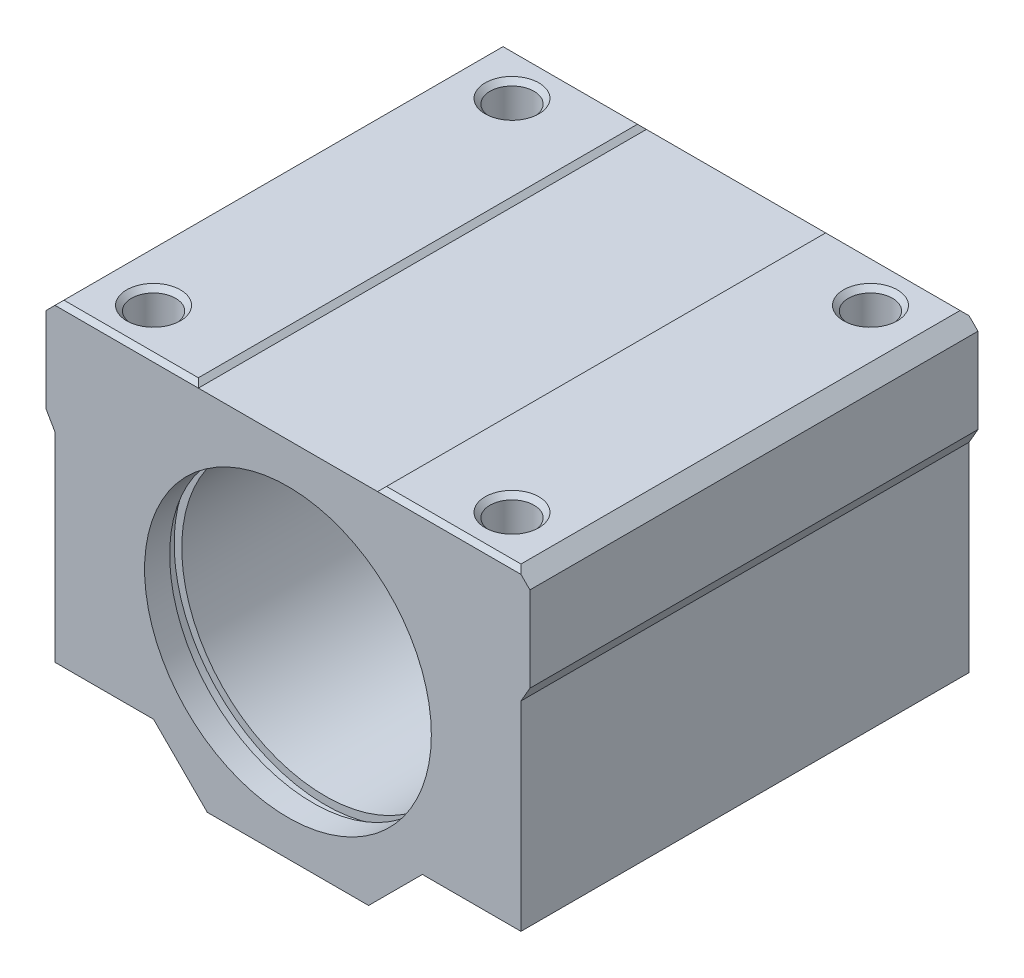
SolidWorks part; units mm, degrees
ref_plane "前视" through (0, 0, 0) normal (0, 0, 1) x (1, 0, 0)
ref_plane "上视" through (0, 0, 0) normal (0, 1, 0) x (1, 0, 0)
ref_plane "右视" through (0, 0, 0) normal (1, 0, 0) x (0, 0, -1)
sketch "草图1" plane through (0, 0, 0) normal (0, 0, 1) x (1, 0, 0)
  line L0 (-27, 19.5) -> (-27, 10)
  line L1 (-27, 10) -> (-26, 8.2679)
  line L2 (-26, 8.2679) -> (-26, -14)
  line L3 (-26, -14) -> (-15, -14)
  line L4 (-15, -14) -> (-9, -20)
  line L5 (-9, -20) -> (9, -20)
  line L6 (9, -20) -> (15, -14)
  line L7 (15, -14) -> (26, -14)
  line L8 (26, -14) -> (26, 8.2679)
  line L9 (26, 8.2679) -> (27, 10)
  line L10 (27, 10) -> (27, 19.5)
  line L11 (27, 19.5) -> (25.5, 21)
  line L12 (25.5, 21) -> (10.5, 21)
  line L13 (10.5, 21) -> (10, 20.5)
  line L14 (10, 20.5) -> (-10, 20.5)
  line L15 (-10, 20.5) -> (-10.5, 21)
  line L16 (-10.5, 21) -> (-25.5, 21)
  line L17 (-25.5, 21) -> (-27, 19.5)
extrude "凸台-拉伸1" add sketch "草图1" along normal blind 50
sketch "草图2" plane through (0, 0, 0) normal (1, 0, 0) x (0, 0, -1)
  line L0 (-62.5, -41) -> (12.5, -41)
  line L1 (12.5, -41) -> (12.5, 41)
  line L2 (12.5, 41) -> (-62.5, 41)
  line L3 (-62.5, 41) -> (-62.5, -41)
  line L4 (-50, -20) -> (0, -20)
  line L5 (0, -20) -> (0, 20.5)
  line L6 (0, 20.5) -> (-0.5, 21)
  line L7 (-0.5, 21) -> (-49.5, 21)
  line L8 (-49.5, 21) -> (-50, 20.5)
  line L9 (-50, 20.5) -> (-50, -20)
extrude "切除-拉伸1" cut sketch "草图2" along normal blind 27 and the other way blind 27
sketch "草图3" plane through (0, 0, 0) normal (1, 0, 0) x (0, 0, -1)
  line L0 (-50, 0) -> (-50, 16)
  line L1 (-50, 16) -> (-47.2, 16)
  line L2 (-47.2, 16) -> (-47.2, 16.85)
  line L3 (-47.2, 16.85) -> (-45.85, 16.85)
  line L4 (-45.85, 16.85) -> (-45.85, 16)
  line L5 (-45.85, 16) -> (-4.15, 16)
  line L6 (-4.15, 16) -> (-4.15, 16.85)
  line L7 (-4.15, 16.85) -> (-2.8, 16.85)
  line L8 (-2.8, 16.85) -> (-2.8, 16)
  line L9 (-2.8, 16) -> (0, 16)
  line L10 (0, 16) -> (0, 0)
  line L11 (0, 0) -> (-50, 0)
  line L12 (0, 0) -> (-50, 0) construction
revolve "切除-旋转1" cut sketch "草图3" angle 360 about L12 reverse direction yes
ref_plane "基准面1" through (20, 0, 0) normal (1, 0, 0) x (0, 0, -1)
sketch "草图4" plane through (20, 0, 0) normal (1, 0, 0) x (0, 0, -1)
  line L0 (-5, 21) -> (-2, 21)
  line L1 (-2, 21) -> (-2.5415, 20.4585)
  line L2 (-2.5415, 20.4585) -> (-2.5415, 9)
  line L3 (-2.5415, 9) -> (-2.4, 9)
  line L4 (-2.4, 9) -> (-2.4, -13.5)
  line L5 (-2.4, -13.5) -> (-2.1113, -14)
  line L6 (-2.1113, -14) -> (-5, -14)
  line L7 (-5, -14) -> (-5, 21)
  line L8 (-5, -14) -> (-5, 21) construction
revolve "切除-旋转2" cut sketch "草图4" angle 360 about L8 reverse direction yes
cosmetic thread "装饰螺纹线1" parameters "D1"=12, "D2"=6
sketch "草图5" plane through (20, 0, 0) normal (1, 0, 0) x (0, 0, -1)
  line L0 (-45, 21) -> (-42, 21)
  line L1 (-42, 21) -> (-42.5415, 20.4585)
  line L2 (-42.5415, 20.4585) -> (-42.5415, 9)
  line L3 (-42.5415, 9) -> (-42.4, 9)
  line L4 (-42.4, 9) -> (-42.4, -13.5)
  line L5 (-42.4, -13.5) -> (-42.1113, -14)
  line L6 (-42.1113, -14) -> (-45, -14)
  line L7 (-45, -14) -> (-45, 21)
  line L8 (-45, -14) -> (-45, 21) construction
revolve "切除-旋转3" cut sketch "草图5" angle 360 about L8 reverse direction yes
cosmetic thread "装饰螺纹线2" parameters "D1"=12, "D2"=6
ref_plane "基准面2" through (-20, 0, 0) normal (1, 0, 0) x (0, 0, -1)
sketch "草图6" plane through (-20, 0, 0) normal (1, 0, 0) x (0, 0, -1)
  line L0 (-5, 21) -> (-2, 21)
  line L1 (-2, 21) -> (-2.5415, 20.4585)
  line L2 (-2.5415, 20.4585) -> (-2.5415, 9)
  line L3 (-2.5415, 9) -> (-2.4, 9)
  line L4 (-2.4, 9) -> (-2.4, -13.5)
  line L5 (-2.4, -13.5) -> (-2.1113, -14)
  line L6 (-2.1113, -14) -> (-5, -14)
  line L7 (-5, -14) -> (-5, 21)
  line L8 (-5, -14) -> (-5, 21) construction
revolve "切除-旋转4" cut sketch "草图6" angle 360 about L8 reverse direction yes
cosmetic thread "装饰螺纹线3" parameters "D1"=12, "D2"=6
sketch "草图7" plane through (-20, 0, 0) normal (1, 0, 0) x (0, 0, -1)
  line L0 (-45, 21) -> (-42, 21)
  line L1 (-42, 21) -> (-42.5415, 20.4585)
  line L2 (-42.5415, 20.4585) -> (-42.5415, 9)
  line L3 (-42.5415, 9) -> (-42.4, 9)
  line L4 (-42.4, 9) -> (-42.4, -13.5)
  line L5 (-42.4, -13.5) -> (-42.1113, -14)
  line L6 (-42.1113, -14) -> (-45, -14)
  line L7 (-45, -14) -> (-45, 21)
  line L8 (-45, -14) -> (-45, 21) construction
revolve "切除-旋转5" cut sketch "草图7" angle 360 about L8 reverse direction yes
cosmetic thread "装饰螺纹线4" parameters "D1"=12, "D2"=6
ref_plane "基准面3" through (0, 0, 25) normal (0, 0, 1) x (1, 0, 0)
ref_plane "body_to_bushing XY" through (0, 0, 25) normal (0, 0, -1) x (-1, 0, 0)
ref_plane "body_to_bushing XZ" through (0, 0, 0) normal (0, 1, 0) x (1, 0, 0)
ref_plane "body_to_bushing YZ" through (0, 0, 0) normal (1, 0, 0) x (0, 0, -1)
ref_axis "body_to_bushing X" through (-80.9, 0, 25) along (1, 0, 0)
ref_axis "body_to_bushing Y" through (0, 50, 25) along (0, -1, 0)
ref_axis "body_to_bushing Z" through (0, 0, -80.9) along (0, 0, 1)
sketch3d "body_to_bushing"
  point P0 (0, 0, 25)
